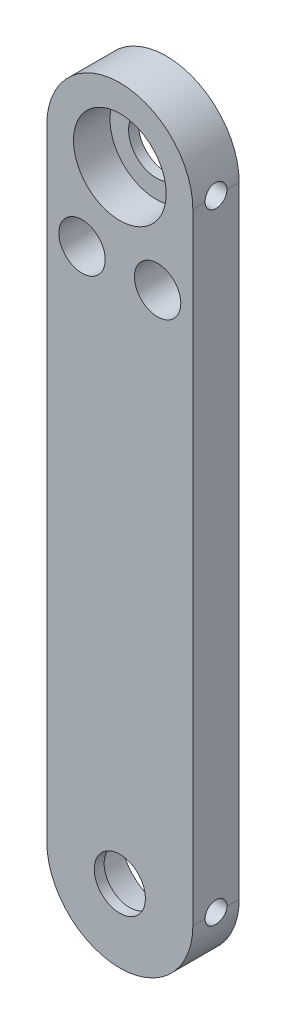
SolidWorks part; units mm, degrees
ref_plane "Alzado" through (0, 0, 0) normal (0, 0, 1) x (1, 0, 0)
ref_plane "Planta" through (0, 0, 0) normal (0, 1, 0) x (1, 0, 0)
ref_plane "Vista lateral" through (0, 0, 0) normal (1, 0, 0) x (0, 0, -1)
sketch "Croquis1" plane through (0, 0, 0) normal (0, 0, 1) x (1, 0, 0)
  line L0 (0, 42.5) -> (0, -42.5) construction
  line L1 (10, 42.5) -> (10, -42.5)
  line L2 (-10, 42.5) -> (-10, -42.5)
  arc A0 (10, 42.5) -> (-10, 42.5) centre (0, 42.5) ccw
  arc A1 (-10, -42.5) -> (10, -42.5) centre (0, -42.5) ccw
  point P2 (0, 0)
  point P8 (0, 52.5)
  point P9 (0, -52.5)
  dimension "D1" = 105
  dimension "D2" = 20
extrude "Saliente-Extruir1" add sketch "Croquis1" along normal blind 6.35
sketch "Croquis2" plane through (0, 0, 6.35) normal (0, 0, 1) x (1, 0, 0)
  circle A0 centre (0, 42.5) radius 6.35
  dimension "D1" = 12.7
extrude "Cortar-Extruir1" cut sketch "Croquis2" against normal blind 5
sketch "Croquis3" plane through (0, 0, 1.35) normal (0, 0, 1) x (1, 0, 0)
  circle A0 centre (0, 42.5) radius 3.8
  dimension "D1" = 7.6
extrude "Cortar-Extruir2" cut sketch "Croquis3" against normal through all
sketch "Croquis4" plane through (0, 0, 6.35) normal (0, 0, 1) x (1, 0, 0)
  line L0 (0, 42.5) -> (0, 30.5) construction
  line L1 (0, 30.5) -> (2, 30.5) construction
  circle A0 centre (5.175, 30.5) radius 3.175
  circle A1 centre (-5.175, 30.5) radius 3.175
  dimension "D3" = 6.35
  dimension "D1" = 2
  dimension "D2" = 12
extrude "Cortar-Extruir3" cut sketch "Croquis4" against normal blind 5
sketch "Croquis5" plane through (0, 0, 1.35) normal (0, 0, 1) x (1, 0, 0)
  circle A0 centre (-5.175, 30.5) radius 1.5
  circle A1 centre (5.175, 30.5) radius 1.5
  dimension "D1" = 3
  dimension "D2" = 3
extrude "Cortar-Extruir4" cut sketch "Croquis5" against normal blind 5
sketch "Croquis6" plane through (10, 0, 0) normal (1, 0, 0) x (0, 0, -1)
  line L0 (-6.35, 42.5) -> (0, 42.5) construction
  circle A0 centre (-3.175, 42.5) radius 1.5
  dimension "D1" = 3
extrude "Cortar-Extruir5" cut sketch "Croquis6" against normal blind 5
sketch "Croquis7" plane through (0, 0, 0) normal (0, 0, -1) x (-1, 0, 0)
  circle A0 centre (0, -42.5) radius 6.35
  dimension "D1" = 12.7
extrude "Cortar-Extruir6" cut sketch "Croquis7" against normal blind 5
sketch "Croquis8" plane through (0, 0, 5) normal (0, 0, -1) x (-1, 0, 0)
  circle A0 centre (0, -42.5) radius 3.5
  dimension "D1" = 7
extrude "Cortar-Extruir7" cut sketch "Croquis8" against normal blind 5
sketch "Croquis9" plane through (10, 0, 0) normal (1, 0, 0) x (0, 0, -1)
  line L0 (-6.35, -42.5) -> (0, -42.5) construction
  circle A0 centre (-3.175, -42.5) radius 1.5
  dimension "D1" = 3
extrude "Cortar-Extruir8" cut sketch "Croquis9" against normal blind 5
ref_axis "Eje1" through (0, 42.5, 1.35) along (0, 0, 1)
ref_axis "Eje2" through (0, -42.5, 5) along (0, 0, -1)
